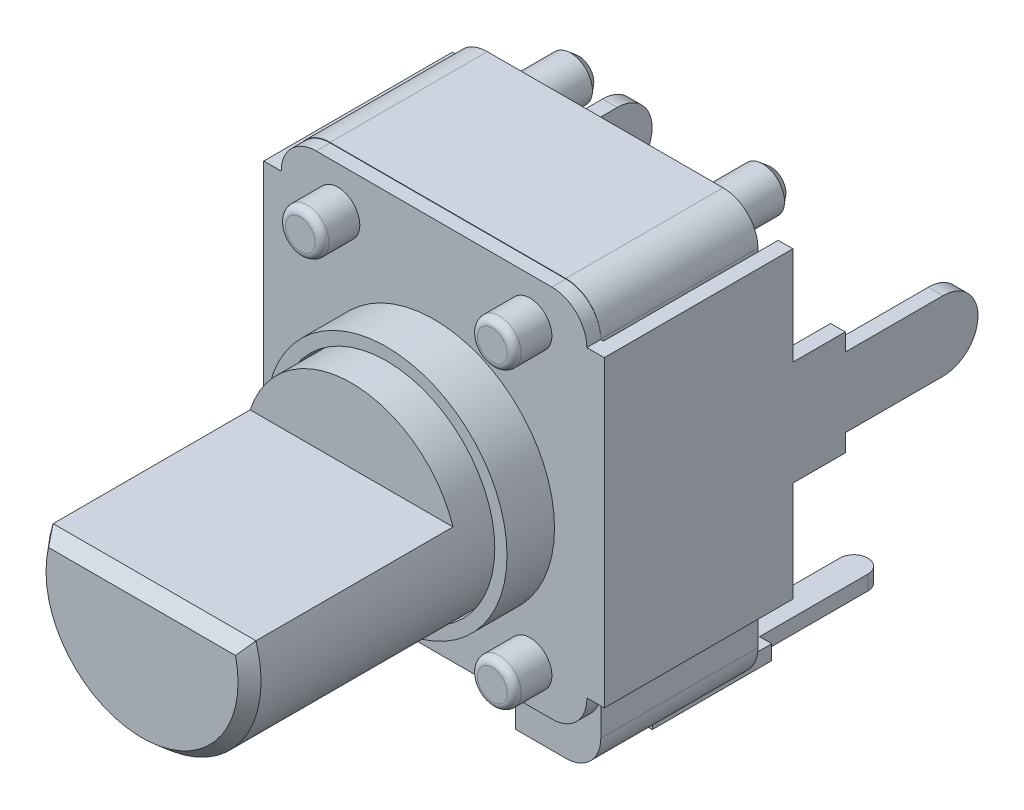
SolidWorks part; units mm, degrees
ref_plane "Plan de face" through (0, 0, 0) normal (0, 0, 1) x (1, 0, 0)
ref_plane "Plan de dessus" through (0, 0, 0) normal (0, 1, 0) x (1, 0, 0)
ref_plane "Plan de droite" through (0, 0, 0) normal (1, 0, 0) x (0, 0, -1)
sketch "Esquisse2" plane through (0, 0, 0) normal (0, 0, 1) x (1, 0, 0)
  line L1 (-3.375, 5.95) -> (3.375, 5.95)
  line L2 (-4.375, 4.95) -> (-4.375, -4.95)
  line L3 (-3.375, -5.95) -> (3.375, -5.95)
  line L4 (4.375, 4.95) -> (4.375, -4.95)
  arc A0 (-3.375, 5.95) -> (-4.375, 4.95) centre (-3.375, 4.95) ccw
  arc A1 (3.375, 5.95) -> (4.375, 4.95) centre (3.375, 4.95) cw
  arc A2 (3.375, -5.95) -> (4.375, -4.95) centre (3.375, -4.95) ccw
  arc A3 (-4.375, -4.95) -> (-3.375, -5.95) centre (-3.375, -4.95) ccw
  point P7 (-4.375, 5.95)
  point P10 (4.375, 5.95)
  point P15 (-4.375, -5.95)
  dimension "D5" = 1
  dimension "D1" = 11.9
  dimension "D2" = 8.75
  dimension "D3" = 4.375
  dimension "D4" = 5.95
extrude "Extrusion1" add sketch "Esquisse2" along normal blind 4.5
sketch "Esquisse3" plane through (0, 0, 4.5) normal (0, 0, 1) x (1, 0, 0)
  line L0 (3.375, 5.95) -> (-3.375, 5.95) construction
  line L1 (-4.375, 4.95) -> (-4.375, -4.95) construction
  line L2 (4.375, -4.95) -> (4.375, 4.95) construction
  circle A0 centre (-2.75, 4.725) radius 0.625
  circle A1 centre (2.75, 4.725) radius 0.625
  circle A2 centre (2.75, -3.695) radius 0.625
  circle A3 centre (-2.75, -3.695) radius 0.625
  dimension "D1" = 1.225
  dimension "D2" = 1.625
  dimension "D3" = 1.625
  dimension "D4" = 8.42
extrude "Extrusion2" add sketch "Esquisse3" along normal blind 1.48 and the other way blind 6.5
fillet "Congé1" radius 0.2 4 edges at (3.375, -3.695, 5.98) (-2.125, -3.695, 5.98) (3.375, 4.725, 5.98) (-2.125, 4.725, 5.98)
chamfer "Chanfrein1" distance 0.2 angle 50 4 edges at (3.375, -3.695, -2) (-2.125, -3.695, -2) (-2.125, 4.725, -2) (3.375, 4.725, -2) first distance on face at (3.375, -3.695, -2) first distance on face at (-2.125, -3.695, -2) first distance on face at (-2.125, 4.725, -2) first distance on face at (3.375, 4.725, -2)
sketch "Esquisse4" plane through (0, 0, 4.5) normal (0, 0, 1) x (1, 0, 0)
  line L1 (-1.94, -5.95) -> (1.94, -5.95)
  line L2 (-1.94, -5.95) -> (-1.94, -4.75)
  line L3 (-1.94, -4.75) -> (1.94, -4.75)
  line L4 (1.94, -5.95) -> (1.94, -4.75)
  dimension "D1" = 3.88
  dimension "D2" = 1.2
  dimension "D3" = 1.94
extrude "Enlèv. mat.-Extru.1" cut sketch "Esquisse4" against normal blind 1.5
sketch "Esquisse5" plane through (0, 0, 4.5) normal (0, 0, 1) x (1, 0, 0)
  line L1 (-3.3759, 5.9371) -> (0, 5.9371)
  line L2 (-4.3759, 4.9371) -> (-4.8759, 4.9371)
  line L3 (-3.3762, -4.775) -> (0, -4.775)
  line L6 (0, 5.9371) -> (0, -4.775)
  line L7 (-4.8759, 4.9371) -> (-4.8759, -3.75)
  line L8 (-4.8759, -3.75) -> (-4.3759, -3.75)
  arc A0 (-3.3759, 5.9371) -> (-4.3759, 4.9371) centre (-3.3759, 4.9371) ccw
  arc A3 (-4.3759, -3.75) -> (-3.3762, -4.775) centre (-3.3762, -3.775) ccw
  point P7 (-4.3759, 5.95)
  point P10 (4.3741, 5.95)
  point P15 (-4.3759, -4.75)
  dimension "D5" = 1
  dimension "D1" = 10.7
  dimension "D2" = 8.75
extrude "Extrusion3" add sketch "Esquisse5" along normal blind 0.4
sketch "Esquisse8" plane through (0, 0, 4.5) normal (0, 0, -1) x (-1, 0, 0)
  line L0 (4.3759, 4.9371) -> (4.8759, 4.9371) construction
  line L1 (4.8759, -3.75) -> (4.4558, -3.75)
  line L2 (4.8759, -3.75) -> (4.8759, 4.9371)
  line L3 (4.8759, 4.9371) -> (4.4558, 4.9371)
  line L4 (4.4558, -3.75) -> (4.4558, 4.9371)
extrude "Extrusion4" add sketch "Esquisse8" along normal blind 5
sketch "Esquisse9" plane through (-4.4558, 0, 0) normal (1, 0, 0) x (0, 0, -1)
  line L1 (0.4962, -2.7) -> (0.0715, -2.7)
  line L2 (0.4962, -2.7) -> (0.4962, -1.45)
  line L3 (0.4962, -1.45) -> (0.0715, -1.45)
  line L4 (0.0715, -2.7) -> (0.0715, -1.45)
  line L7 (0.4964, 2.7) -> (0.0718, 2.7)
  line L8 (0.4964, 2.7) -> (0.4964, 3.95)
  line L9 (0.4964, 3.95) -> (0.0718, 3.95)
  line L10 (0.0718, 2.7) -> (0.0718, 3.95)
  line L13 (-4.5, 5.95) -> (0, 5.95) construction
  line L14 (-4.5, -5.95) -> (0, -5.95) construction
  dimension "D1" = 1.25
  dimension "D2" = 3.25
  dimension "D3" = 1.25
  dimension "D4" = 2
extrude "Extrusion5" add sketch "Esquisse9" along normal blind 2.5
fillet "Congé3" radius 0.5 2 edges at (-1.9558, -2.7, -0.2838) (-1.9558, -1.45, -0.2838)
fillet "Congé4" radius 0.5 2 edges at (-1.9558, 2.7, -0.2841) (-1.9558, 3.95, -0.2841)
sketch "Esquisse11" plane through (0, 0, 4.9) normal (0, 0, 1) x (1, 0, 0)
  circle A0 centre (0, 0) radius 3.45
extrude "Extrusion6" add sketch "Esquisse11" along normal blind 1.36
sketch "Esquisse12" plane through (0, 0, 6.26) normal (0, 0, 1) x (1, 0, 0)
  circle A0 centre (0, 0) radius 3.1
extrude "Enlèv. mat.-Extru.2" cut sketch "Esquisse12" against normal blind 4
sketch "Esquisse13" plane through (0, 0, 2.26) normal (0, 0, 1) x (1, 0, 0)
  circle A0 centre (0, 0) radius 3.05
extrude "Extrusion7" add sketch "Esquisse13" along normal blind 11
sketch "Esquisse14" plane through (0, 0, 13.26) normal (0, 0, 1) x (1, 0, 0)
  line L1 (-3.5555, 0.9326) -> (3.5808, 0.9326)
  line L2 (-3.5555, 0.9326) -> (-3.5555, 3.5006)
  line L3 (-3.5555, 3.5006) -> (3.5808, 3.5006)
  line L4 (3.5808, 0.9326) -> (3.5808, 3.5006)
extrude "Enlèv. mat.-Extru.7" cut sketch "Esquisse14" against normal blind 6
chamfer "Chanfrein2" distance 0.3 angle 50 2 edges at (0, -3.05, 13.26) (0, 0.9326, 13.26) first distance on face at (0, -1.0587, 13.26)
sketch "Esquisse15" plane through (0, -5.95, 0) normal (0, -1, 0) x (1, 0, 0)
  line L0 (-3.375, 0) -> (3.375, 0) construction
  line L1 (-0.75, 1.9) -> (0.75, 1.9)
  line L2 (-0.75, 1.9) -> (-0.75, 1.48)
  line L3 (-0.75, 1.48) -> (0.75, 1.48)
  line L4 (0.75, 1.9) -> (0.75, 1.48)
  line L5 (1.75, 1.9) -> (3.25, 1.9)
  line L6 (1.75, 1.9) -> (1.75, 1.48)
  line L7 (1.75, 1.48) -> (3.25, 1.48)
  line L8 (3.25, 1.9) -> (3.25, 1.48)
  line L9 (-3.25, 1.9) -> (-1.75, 1.9)
  line L10 (-3.25, 1.9) -> (-3.25, 1.48)
  line L11 (-3.25, 1.48) -> (-1.75, 1.48)
  line L12 (-1.75, 1.9) -> (-1.75, 1.48)
  point P10 (0, 0)
  point P15 (0, 0)
  dimension "D1" = 1.5
  dimension "D2" = 0.42
  dimension "D3" = 1.9
  dimension "D4" = 2.5
  dimension "D5" = 1.5
  dimension "D6" = 3.25
  dimension "D7" = 3.25
  dimension "D8" = 1.5
extrude "Extrusion8" add sketch "Esquisse15" along normal blind 0.65
sketch "Esquisse16" plane through (0, 0, 1.48) normal (0, 0, -1) x (-1, 0, 0)
  line L0 (1.75, -6.6) -> (1.75, -5.95) construction
  line L1 (3.25, -6.6) -> (1.75, -6.6)
  line L2 (3.25, -6.6) -> (3.25, -6.18)
  line L3 (3.25, -6.18) -> (1.75, -6.18)
  line L4 (1.75, -6.6) -> (1.75, -6.18)
  line L5 (-0.75, -6.6) -> (-0.75, -5.95) construction
  line L6 (0.75, -6.6) -> (-0.75, -6.6)
  line L7 (0.75, -6.6) -> (0.75, -6.18)
  line L8 (0.75, -6.18) -> (-0.75, -6.18)
  line L9 (-0.75, -6.6) -> (-0.75, -6.18)
  line L10 (-3.25, -6.6) -> (-3.25, -5.95) construction
  line L11 (-1.75, -6.6) -> (-3.25, -6.6)
  line L12 (-1.75, -6.6) -> (-1.75, -6.18)
  line L13 (-1.75, -6.18) -> (-3.25, -6.18)
  line L14 (-3.25, -6.6) -> (-3.25, -6.18)
extrude "Extrusion9" add sketch "Esquisse16" along normal blind 3
sketch "Esquisse17" plane through (0, 0, -1.52) normal (0, 0, -1) x (-1, 0, 0)
  line L0 (3.25, -6.18) -> (1.75, -6.18) construction
  line L1 (2.9, -6.18) -> (2.1, -6.18)
  line L2 (2.9, -6.18) -> (2.9, -6.6)
  line L3 (2.9, -6.6) -> (2.1, -6.6)
  line L4 (2.1, -6.18) -> (2.1, -6.6)
  line L5 (1.75, -6.6) -> (3.25, -6.6) construction
  line L6 (1.75, -6.18) -> (1.75, -6.6) construction
  line L8 (-0.75, -6.6) -> (0.75, -6.6) construction
  line L9 (0.4, -6.6) -> (-0.4, -6.6)
  line L10 (0.4, -6.6) -> (0.4, -6.18)
  line L11 (0.4, -6.18) -> (-0.4, -6.18)
  line L12 (-0.4, -6.6) -> (-0.4, -6.18)
  line L13 (0.75, -6.18) -> (-0.75, -6.18) construction
  line L14 (-0.75, -6.18) -> (-0.75, -6.6) construction
  line L15 (-3.25, -6.6) -> (-1.75, -6.6) construction
  line L16 (-2.1, -6.6) -> (-2.9, -6.6)
  line L17 (-2.1, -6.6) -> (-2.1, -6.18)
  line L18 (-2.1, -6.18) -> (-2.9, -6.18)
  line L19 (-2.9, -6.6) -> (-2.9, -6.18)
  line L20 (-1.75, -6.18) -> (-3.25, -6.18) construction
  line L21 (-3.25, -6.18) -> (-3.25, -6.6) construction
  dimension "D1" = 0.8
  dimension "D2" = 0.35
  dimension "D3" = 0.8
  dimension "D4" = 0.35
  dimension "D5" = 0.35
  dimension "D6" = 0.8
extrude "Extrusion10" add sketch "Esquisse17" along normal blind 3.5
fillet "Congé5" radius 0.4 6 edges at (2.9, -6.39, -5.02) (-2.1, -6.39, -5.02) (0.4, -6.39, -5.02) (-2.9, -6.39, -5.02) (-0.4, -6.39, -5.02) (2.1, -6.39, -5.02)
sketch "Esquisse18" plane through (0, 0, -0.5) normal (0, 0, -1) x (-1, 0, 0)
  line L1 (4.4558, 4.9371) -> (4.4558, -3.75) construction
  line L2 (4.4558, 2.125) -> (4.8759, 2.125)
  line L3 (4.4558, 2.125) -> (4.4558, -0.875)
  line L4 (4.4558, -0.875) -> (4.8759, -0.875)
  line L6 (4.8759, 2.125) -> (4.8759, -0.875)
  line L7 (4.8759, -3.75) -> (4.8759, 4.9371) construction
  line L8 (2.4558, 2.7) -> (4.4558, 2.7) construction
  line L9 (2.4558, -1.45) -> (4.4558, -1.45) construction
  dimension "D1" = 0.575
  dimension "D2" = 3
  dimension "D3" = 0.575
extrude "Extrusion11" add sketch "Esquisse18" along normal blind 1.5
sketch "Esquisse19" plane through (0, 0, -2) normal (0, 0, -1) x (-1, 0, 0)
  line L1 (4.4558, 2.125) -> (4.4558, -0.875) construction
  line L2 (4.4558, 1.625) -> (4.8759, 1.625)
  line L3 (4.4558, 1.625) -> (4.4558, -0.375)
  line L4 (4.4558, -0.375) -> (4.8759, -0.375)
  line L6 (4.8759, 1.625) -> (4.8759, -0.375)
  line L7 (4.8759, -0.875) -> (4.8759, 2.125) construction
  line L8 (4.4558, -0.875) -> (4.8759, -0.875) construction
  dimension "D1" = 2
  dimension "D2" = 0.5
extrude "Extrusion12" add sketch "Esquisse19" along normal blind 3.8
fillet "Congé6" radius 1 2 edges at (-4.6658, -0.375, -5.8) (-4.6658, 1.625, -5.8)
mirror "Symétrie1" of "Congé6", "Extrusion12", "Extrusion11", "Extrusion5", "Extrusion4", "Extrusion3", "Congé3", "Congé4"
